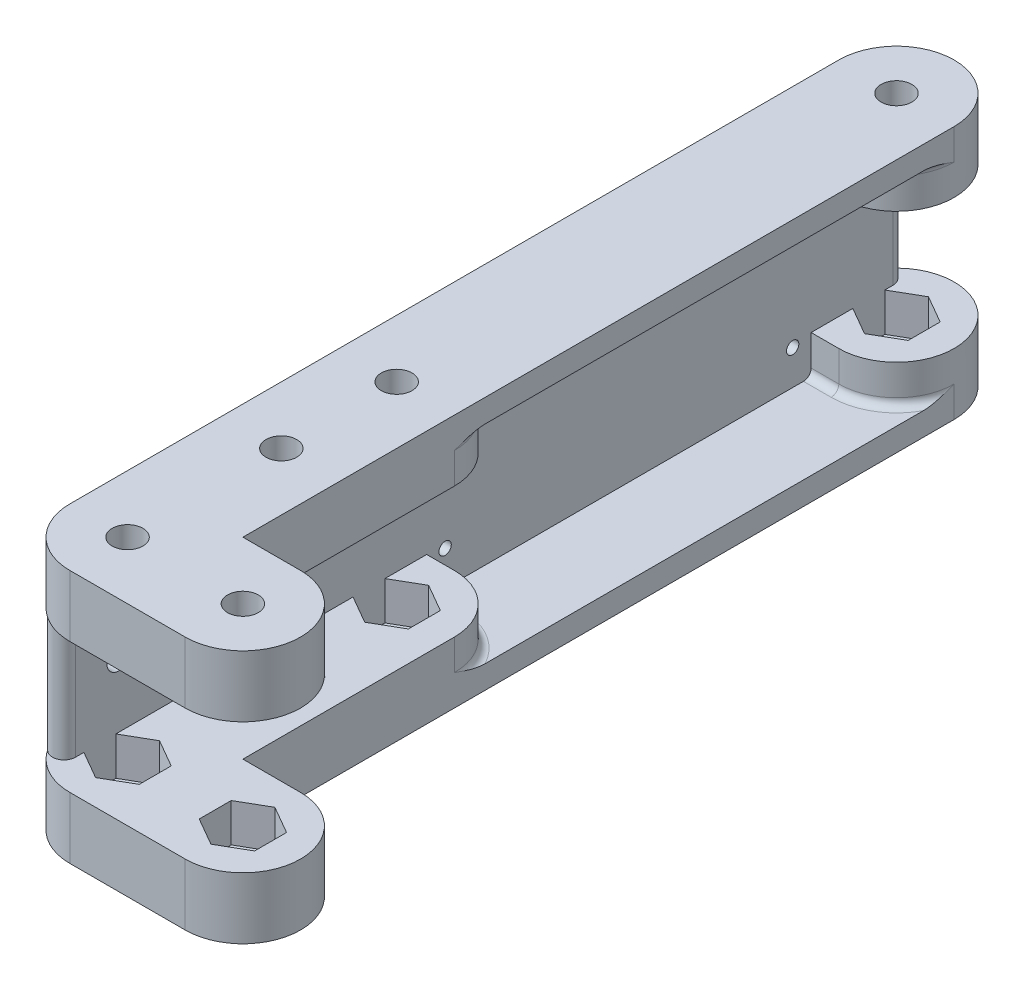
SolidWorks part; units mm, degrees
material "ABS"
ref_plane "前视基准面" through (0, 0, 0) normal (0, 0, 1) x (1, 0, 0)
ref_plane "上视基准面" through (0, 0, 0) normal (0, 1, 0) x (1, 0, 0)
ref_plane "右视基准面" through (0, 0, 0) normal (1, 0, 0) x (0, 0, -1)
sketch "草图1" plane through (0, 0, 0) normal (0, 1, 0) x (1, 0, 0)
  line L0 (0, 127.6556) -> (0, 0) construction
  line L1 (0, 0) -> (15, 0) construction
  line L3 (7.5, 7.5) -> (15, 7.5)
  line L4 (-7.5, 100) -> (-7.5, 0)
  line L5 (7.5, 100) -> (7.5, 7.5)
  line L7 (15, -7.5) -> (0, -7.5)
  line L9 (3.6, 97.9215) -> (3.6, 102.0785) construction
  line L10 (3.6, 102.0785) -> (0, 104.1569) construction
  line L11 (0, 104.1569) -> (-3.6, 102.0785) construction
  line L12 (-3.6, 102.0785) -> (-3.6, 97.9215) construction
  line L13 (-3.6, 97.9215) -> (0, 95.8431) construction
  line L14 (0, 95.8431) -> (3.6, 97.9215) construction
  circle A0 centre (0, 0) radius 2
  circle A1 centre (15, 0) radius 2
  circle A2 centre (0, 20) radius 2
  circle A3 centre (0, 35) radius 2
  circle A4 centre (0, 100) radius 2
  arc A5 (7.5, 100) -> (-7.5, 100) centre (0, 100) ccw
  circle A7 centre (0, 100) radius 3.6 construction
  arc A8 (15, -7.5) -> (15, 7.5) centre (15, 0) ccw
  arc A9 (-7.5, 0) -> (0, -7.5) centre (0, 0) ccw
  dimension "D1" = 15
  dimension "D2" = 20
  dimension "D3" = 15
  dimension "D4" = 65
  dimension "D5" = 4
  dimension "D6" = 7.5
  dimension "D8" = 7.2
extrude "凸台-拉伸1" add sketch "草图1" along normal mid plane 33
sketch "草图3" plane through (0, 0, 0) normal (0, 1, 0) x (1, 0, 0)
  line L0 (-7.5, 100) -> (-7.5, 0) construction
  line L1 (0, -7.5) -> (15, -7.5) construction
  line L2 (15, 7.5) -> (7.5, 7.5) construction
  line L3 (7.5, 7.5) -> (7.5, 100) construction
  line L4 (-3.6, -7.5) -> (15, -7.5)
  line L7 (-3.6, 106.5795) -> (-3.6, -7.5)
  line L8 (15, 7.5) -> (7.5, 7.5)
  line L9 (7.5, 7.5) -> (7.5, 100)
  arc A1 (15, -7.5) -> (15, 7.5) centre (15, 0) ccw construction
  arc A4 (7.5, 100) -> (-7.5, 100) centre (0, 100) ccw construction
  arc A5 (15, -7.5) -> (15, 7.5) centre (15, 0) ccw
  arc A6 (7.5, 100) -> (-3.6, 106.5795) centre (0, 100) ccw
  dimension "D1" = 3.9
extrude "切除-拉伸1" cut sketch "草图3" against normal offset from surface 8 and the other way offset from surface 8 up to face at (5.1352, -16.5, -29.421) other way up to face at (0, 16.5, -33)
sketch "草图4" plane through (0, 0, 0) normal (0, 1, 0) x (1, 0, 0)
  line L0 (-3.6, 92.5) -> (-3.6, 42.5)
  line L1 (7.5, 7.5) -> (7.5, 100) construction
  line L2 (7.5, 35) -> (7.5, 100)
  line L3 (-7.5, 100) -> (-7.5, 0) construction
  line L4 (-3.6, 92.5) -> (0, 92.5)
  line L5 (-3.6, 42.5) -> (0, 42.5)
  arc A0 (7.5, 35) -> (0, 42.5) centre (0, 35) ccw
  arc A2 (7.5, 100) -> (-7.5, 100) centre (0, 100) ccw construction
  arc A3 (0, 92.5) -> (7.5, 100) centre (0, 100) ccw
  dimension "D1" = 3.9
extrude "切除-拉伸2" cut sketch "草图4" along normal offset from surface 3 and the other way offset from surface 3 up to face at (0, 16.5, -33) other way up to face at (5.1352, -16.5, -29.421)
sketch "草图5" plane through (0, 0, 0) normal (0, 1, 0) x (1, 0, 0)
  line L0 (0, 104.1569) -> (-3.6, 102.0785) construction
  line L1 (-3.6, 102.0785) -> (-3.6, 97.9215) construction
  line L2 (-3.6, 97.9215) -> (0, 95.8431) construction
  line L3 (0, 95.8431) -> (3.6, 97.9215) construction
  line L4 (3.6, 97.9215) -> (3.6, 102.0785) construction
  line L5 (3.6, 102.0785) -> (0, 104.1569) construction
  line L6 (0, 104.1569) -> (-3.6, 102.0785)
  line L7 (-3.6, 102.0785) -> (-3.6, 97.9215)
  line L8 (-3.6, 97.9215) -> (0, 95.8431)
  line L9 (0, 95.8431) -> (3.6, 97.9215)
  line L10 (3.6, 97.9215) -> (3.6, 102.0785)
  line L11 (3.6, 102.0785) -> (0, 104.1569)
  line L14 (-3.6, 37.0785) -> (-3.6, 32.9215)
  line L15 (-3.6, 32.9215) -> (0, 30.8431)
  line L16 (0, 30.8431) -> (3.6, 32.9215)
  line L17 (3.6, 32.9215) -> (3.6, 37.0785)
  line L18 (3.6, 37.0785) -> (0, 39.1569)
  line L19 (0, 39.1569) -> (-3.6, 37.0785)
  line L20 (-3.6, 22.0785) -> (-3.6, 17.9215)
  line L21 (-3.6, 17.9215) -> (0, 15.8431)
  line L22 (0, 15.8431) -> (3.6, 17.9215)
  line L23 (3.6, 17.9215) -> (3.6, 22.0785)
  line L24 (3.6, 22.0785) -> (0, 24.1569)
  line L25 (0, 24.1569) -> (-3.6, 22.0785)
  line L26 (-3.6, 2.0785) -> (-3.6, -2.0785)
  line L27 (-3.6, -2.0785) -> (0, -4.1569)
  line L28 (0, -4.1569) -> (3.6, -2.0785)
  line L29 (3.6, -2.0785) -> (3.6, 2.0785)
  line L30 (3.6, 2.0785) -> (0, 4.1569)
  line L31 (0, 4.1569) -> (-3.6, 2.0785)
  line L32 (11.4, 2.0785) -> (11.4, -2.0785)
  line L33 (11.4, -2.0785) -> (15, -4.1569)
  line L34 (15, -4.1569) -> (18.6, -2.0785)
  line L35 (18.6, -2.0785) -> (18.6, 2.0785)
  line L36 (18.6, 2.0785) -> (15, 4.1569)
  line L37 (15, 4.1569) -> (11.4, 2.0785)
  circle A0 centre (0, 100) radius 3.6 construction
  circle A1 centre (0, 100) radius 3.6 construction
  circle A2 centre (0, 35) radius 3.6 construction
  circle A3 centre (0, 20) radius 3.6 construction
  circle A4 centre (0, 0) radius 3.6 construction
  circle A5 centre (15, 0) radius 3.6 construction
extrude "切除-拉伸3" cut sketch "草图5" along normal offset from surface 3 and the other way offset from surface 3 up to face at (0, 16.5, -33) other way up to face at (5.1352, -16.5, -29.421)
sketch "草图6" plane through (-3.6, 0, 0) normal (1, 0, 0) x (0, 0, -1)
  line L0 (44.9, 9) -> (90.1, -9) construction
  line L1 (44.9, 9) -> (90.1, 9) construction
  line L2 (44.9, 9) -> (44.9, -9) construction
  line L3 (44.9, -9) -> (90.1, -9) construction
  line L4 (90.1, 9) -> (90.1, -9) construction
  line L5 (42.5, -13.5) -> (92.5, 13.5) construction
  line L7 (-7.5, -8.5) -> (-7.5, -16.5) construction
  circle A0 centre (44.9, 9) radius 0.8
  circle A1 centre (44.9, -9) radius 0.8
  circle A2 centre (90.1, -9) radius 0.8
  circle A3 centre (90.1, 9) radius 0.8
  circle A4 centre (2.5, 0) radius 1.6
  point P12 (67.5, 0)
  point P13 (67.5, 0)
  dimension "D3" = 1.6
  dimension "D4" = 3.2
  dimension "D5" = 10
  dimension "D1" = 18
  dimension "D2" = 45.2
extrude "切除-拉伸4" cut sketch "草图6" against normal through all
fillet "圆角1" radius 1 8 edges at (5.3033, -13.5, -40.3033) (5.3033, -13.5, -94.6967) (5.3033, 13.5, -94.6967) (5.3033, 13.5, -40.3033) (-1.8, -13.5, -42.5) (-1.8, -13.5, -92.5) (-1.8, 13.5, -92.5) (-1.8, 13.5, -42.5)
fillet "圆角2" radius 1.5 2 edges at (-3.6, 0, 6.5795) (-3.6, 0, -106.5795)
